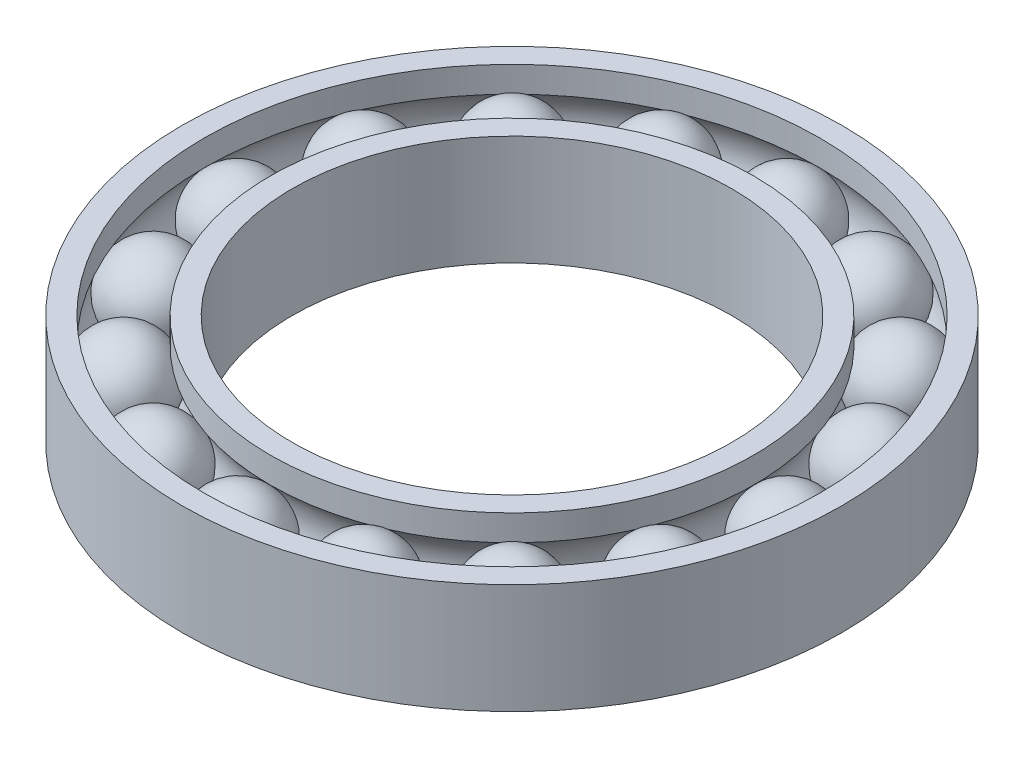
SolidWorks part; units mm, degrees
ref_plane "Front Plane" through (0, 0, 0) normal (0, 0, 1) x (1, 0, 0)
ref_plane "Top Plane" through (0, 0, 0) normal (0, 1, 0) x (1, 0, 0)
ref_plane "Right Plane" through (0, 0, 0) normal (1, 0, 0) x (0, 0, -1)
sketch "Sketch1" plane through (0, 0, 0) normal (1, 0, 0) x (0, 0, -1)
  line L0 (0, -12.5) -> (0, 12.5)
  line L1 (70, 6.6144) -> (70, 12.5)
  line L2 (50, -12.5) -> (55, -12.5)
  line L3 (50, -12.5) -> (50, 12.5)
  line L4 (50, 12.5) -> (55, 12.5)
  line L5 (55, -12.5) -> (55, -6.6144)
  line L6 (50, -12.5) -> (55, 12.5) construction
  line L7 (50, 12.5) -> (55, -12.5) construction
  line L8 (70, -12.5) -> (75, -12.5)
  line L9 (70, -12.5) -> (70, -6.6144)
  line L10 (70, 12.5) -> (75, 12.5)
  line L11 (75, -12.5) -> (75, 12.5)
  line L12 (70, -12.5) -> (75, 12.5) construction
  line L13 (70, 12.5) -> (75, -12.5) construction
  line L14 (55, 6.6144) -> (55, 12.5)
  arc A1 (55, 6.6144) -> (55, -6.6144) centre (62.5, 0) ccw
  arc A2 (70, -6.6144) -> (70, 6.6144) centre (62.5, 0) ccw
  point P0 (52.5, 0)
  point P4 (0, 0)
  point P10 (72.5, 0)
  dimension "D2" = 20
  dimension "D1" = 50
  dimension "D3" = 5
  dimension "D4" = 25
  dimension "D5" = 5
sketch "Sketch2" plane through (0, 0, 0) normal (1, 0, 0) x (0, 0, -1)
  line L0 (70, -12.5) -> (75, 12.5) construction
  line L1 (52.5, 0) -> (72.5, 0)
  arc A0 (52.5, 0) -> (72.5, 0) centre (62.5, 0) cw
revolve "Revolve1" add sketch "Sketch2" angle 360 about L1
revolve "Revolve2" add sketch "Sketch1" angle 360 about L0 region at (0, 0, -72.8297) region at (0, 0, -52.1703)
ref_axis "Axis1" through (0, -8.25, 0) along (0, 1, 0)
pattern_circular "CirPattern2" count 16 over 360 about axis through (0, -8.25, 0) along (0, 1, 0) of bodies 101
